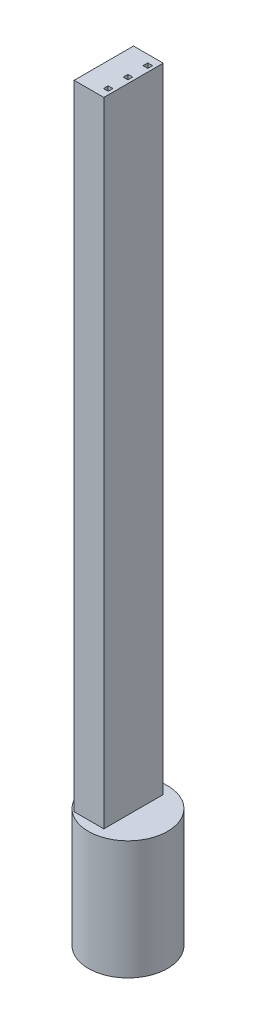
SolidWorks part; units mm, degrees
ref_plane "Front Plane" through (0, 0, 0) normal (0, 0, 1) x (1, 0, 0)
ref_plane "Top Plane" through (0, 0, 0) normal (0, 1, 0) x (1, 0, 0)
ref_plane "Right Plane" through (0, 0, 0) normal (1, 0, 0) x (0, 0, -1)
sketch "Sketch1" plane through (0, 0, 0) normal (0, 0, 1) x (1, 0, 0)
  line L0 (0, 0) -> (-6.35, 0)
  line L1 (-6.35, 0) -> (-6.35, 19.05)
  line L2 (-6.35, 19.05) -> (0, 19.05)
  line L3 (0, 19.05) -> (0, 0)
  dimension "D1" = 19.05
  dimension "D2" = 6.35
revolve "Revolve1" add sketch "Sketch1" angle 360 about L3
sketch "Sketch2" plane through (0, 19.05, 0) normal (0, 1, 0) x (1, 0, 0)
  line L0 (-3.8735, 1.5875) -> (-3.8735, -1.5875)
  line L1 (-3.8735, -1.5875) -> (0.889, -1.5875)
  line L2 (0.889, -1.5875) -> (0.889, 1.5875)
  line L3 (0.889, 1.5875) -> (-3.8735, 1.5875)
  line L4 (0.889, 0) -> (0.381, 0) construction
  line L5 (0.381, 0.381) -> (-0.381, 0.381)
  line L6 (0.381, 0.381) -> (0.381, -0.381)
  line L7 (0.381, -0.381) -> (-0.381, -0.381)
  line L8 (-0.381, 0.381) -> (-0.381, -0.381)
  line L9 (0.381, 0) -> (-0.381, 0) construction
  line L10 (-0.381, 0) -> (-3.8735, 0) construction
  point P10 (0, 0)
  dimension "D1" = 0.508
  dimension "D2" = 0.762
  dimension "D3" = 0.762
  dimension "D4" = 3.175
  dimension "D5" = 4.7625
extrude "Boss-Extrude1" add sketch "Sketch2" along normal blind 101.6
sketch "Sketch6" plane through (0, 19.05, 0) normal (0, 1, 0) x (1, 0, 0)
  line L0 (-0.381, 0.381) -> (-0.381, -0.381)
  line L1 (-0.381, -0.381) -> (0.381, -0.381)
  line L2 (0.381, -0.381) -> (0.381, 0.381)
  line L3 (0.381, 0.381) -> (-0.381, 0.381)
extrude "Cut-Extrude2" cut sketch "Sketch6" against normal blind 6.35
ref_axis "Axis1" through (0, 0, -6.985) along (0, 0, 1)
pattern_linear "LPattern1" count 2 spacing 3.175 along (0, 0, -1) count 2 spacing 3.175 along (0, 0, 1) of "Boss-Extrude1", "Cut-Extrude2"
hole_wizard "1/8 NPT Tapped Hole1" positions "Sketch3" profile "Sketch4" size "1/8" standard "ANSI Inch"
sketch "Sketch3" plane through (0, 0, 0) normal (0, -1, 0) x (-1, 0, 0)
  point P0 (0, 0)
sketch "Sketch4" plane through (0, 0, 0) normal (1, 0, 0) x (0, 0, -1)
  line L0 (0, 0) -> (0, 18.4085)
  line L1 (4.2164, 15.875) -> (0, 18.4085)
  line L2 (-4.2164, 15.875) -> (0, 18.4085) construction
  line L3 (4.2164, 15.875) -> (4.2164, 6.858)
  line L4 (4.2164, 6.858) -> (4.5374, 6.858)
  line L5 (4.5374, 6.858) -> (4.7427, 0)
  line L6 (-4.5374, 6.858) -> (-4.7427, 0) construction
  line L7 (4.7427, 0) -> (0, 0)
  line L8 (0, -6.35) -> (0, 107.95) construction
  line L11 (-4.2164, 6.858) -> (-4.5374, 6.858) construction
  dimension "Tap Drill Dia." = 8.4328
  dimension "Tap Drill Depth" = 15.875
  dimension "Thread Dia." = 9.4855
  dimension "Thread Angle" = 3.43
  dimension "Thread Depth" = 6.858
  dimension "Drill Angle" = 118
cosmetic thread "Hole Thread1" parameters "D1"=6.858, "D2"=10.2827
